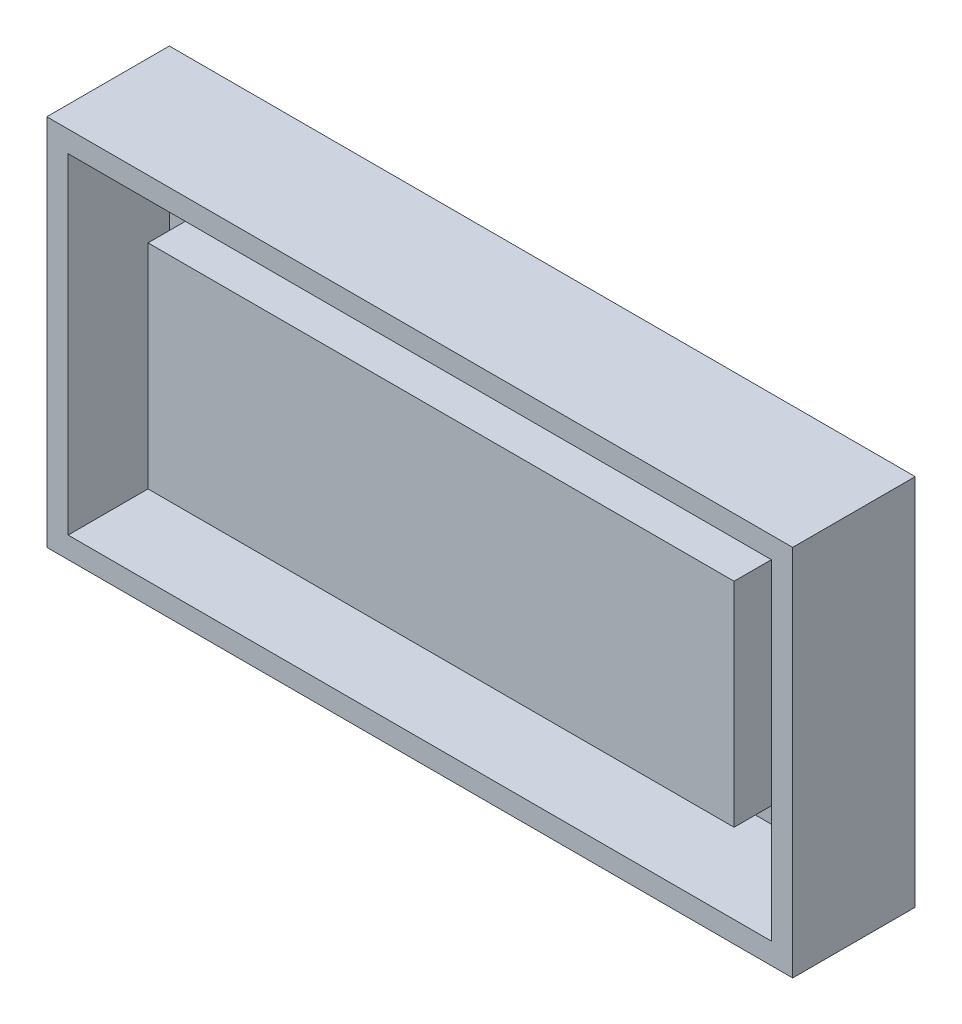
SolidWorks part; units mm, degrees
ref_plane "Front Plane" through (0, 0, 0) normal (0, 0, 1) x (1, 0, 0)
ref_plane "Top Plane" through (0, 0, 0) normal (0, 1, 0) x (1, 0, 0)
ref_plane "Right Plane" through (0, 0, 0) normal (1, 0, 0) x (0, 0, -1)
sketch "Sketch1" plane through (0, 0, 0) normal (0, 0, 1) x (1, 0, 0)
  line L0 (33, 15.5) -> (-33, 15.5)
  line L1 (29, -14.5) -> (-29, -14.5) construction
  line L2 (29, -14.5) -> (29, 14.5) construction
  line L3 (29, 14.5) -> (-29, 14.5) construction
  line L4 (-29, -14.5) -> (-29, 14.5) construction
  line L5 (29, -14.5) -> (-29, 14.5) construction
  line L6 (29, 14.5) -> (-29, -14.5) construction
  line L7 (27.5, -10) -> (-27.5, -10)
  line L8 (27.5, -10) -> (27.5, 10)
  line L9 (27.5, 10) -> (-27.5, 10)
  line L10 (-27.5, -10) -> (-27.5, 10)
  line L11 (27.5, -10) -> (-27.5, 10) construction
  line L12 (27.5, 10) -> (-27.5, -10) construction
  line L13 (35, 17.5) -> (-35, 17.5)
  line L14 (35, 17.5) -> (35, -17.5)
  line L15 (35, -17.5) -> (-35, -17.5)
  line L16 (-35, 17.5) -> (-35, -17.5)
  line L17 (35, 17.5) -> (-35, -17.5) construction
  line L18 (35, -17.5) -> (-35, 17.5) construction
  line L19 (-33, 15.5) -> (-33, -15.5)
  line L20 (33, -15.5) -> (-33, -15.5)
  line L21 (33, 15.5) -> (33, -15.5)
  point P0 (0, 0)
  point P6 (0, 0)
  point P11 (0, 0)
  dimension "D1" = 29
  dimension "D2" = 58
  dimension "D3" = 20
  dimension "D4" = 3
  dimension "D5" = 3
  dimension "D6" = 2
extrude "Boss-Extrude1" add sketch "Sketch1" against normal blind 2 contours L13 L16 L15 L14
extrude "Boss-Extrude2" add sketch "Sketch1<3>" along normal blind 9.5 contours L13 L16 L15 L14 L0 L21 L20 L19 region at (34.2174, 0, 0)
sketch "Sketch1<3>" plane through (0, 0, 0) normal (0, 0, 1) x (1, 0, 0) same geometry as "Sketch1"
extrude "Boss-Extrude3" add sketch "Sketch1<4>" along normal blind 7.5 contours L10 L9 L8 L7
sketch "Sketch1<4>" plane through (0, 0, 0) normal (0, 0, 1) x (1, 0, 0) same geometry as "Sketch1"
